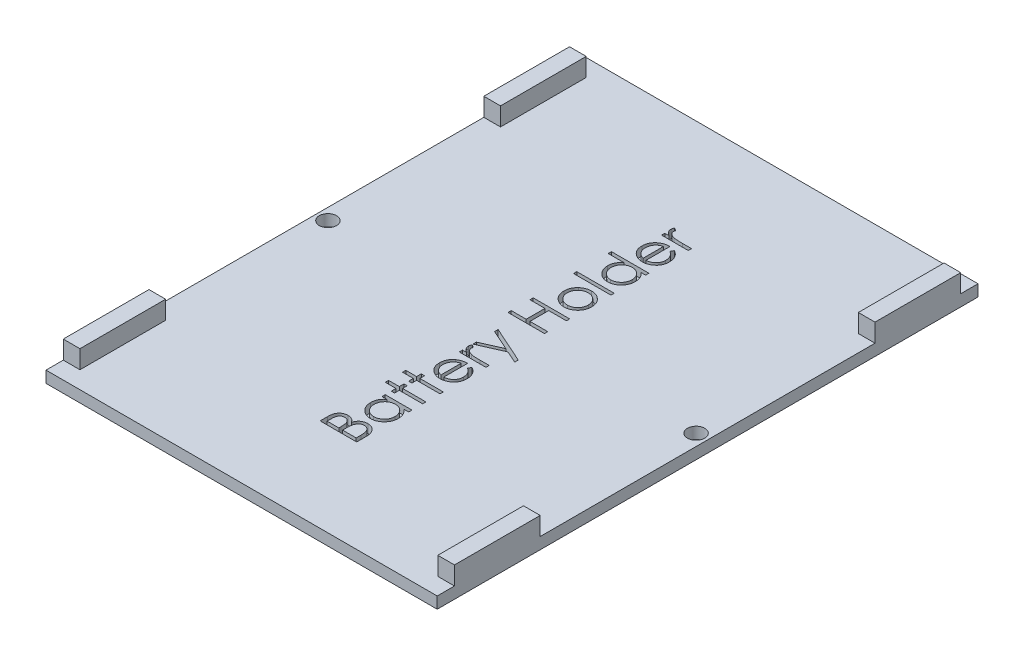
SolidWorks part; units mm, degrees
ref_plane "Front Plane" through (0, 0, 0) normal (0, 0, 1) x (1, 0, 0)
ref_plane "Top Plane" through (0, 0, 0) normal (0, 1, 0) x (1, 0, 0)
ref_plane "Right Plane" through (0, 0, 0) normal (1, 0, 0) x (0, 0, -1)
sketch "Sketch1" plane through (0, 0, 0) normal (0, 1, 0) x (1, 0, 0)
  line L1 (-34, -47) -> (34, -47)
  line L2 (-34, -47) -> (-34, 47)
  line L3 (-34, 47) -> (34, 47)
  line L4 (34, -47) -> (34, 47)
  line L5 (-34, -47) -> (34, 47) construction
  line L6 (-34, 47) -> (34, -47) construction
  point P0 (0, 0)
  dimension "D1" = 68
  dimension "D2" = 94
extrude "Boss-Extrude1" add sketch "Sketch1" along normal blind 2
sketch "Sketch2" plane through (0, 2, 0) normal (0, 1, 0) x (1, 0, 0)
  line L0 (-34, 47) -> (-34, -47) construction
  line L1 (-34, -44) -> (-31.1, -44)
  line L2 (-34, -44) -> (-34, -29.1)
  line L3 (-34, -29.1) -> (-31.1, -29.1)
  line L4 (-31.1, -44) -> (-31.1, -29.1)
  line L5 (-34, -47) -> (34, -47) construction
  dimension "D1" = 14.9
  dimension "D2" = 3
  dimension "D3" = 2.9
extrude "Boss-Extrude2" add sketch "Sketch2" along normal blind 3.175 contours L3 L4 L1 L2
mirror "Mirror1" about plane through (0, 0, 0) normal (1, 0, 0) of "Boss-Extrude2"
mirror "Mirror2" about plane through (0, 0, 0) normal (0, 0, 1) of "Mirror1"
sketch "Sketch3" plane through (0, 2, 0) normal (0, 1, 0) x (1, 0, 0)
  line L0 (3.8196, -31.6351) -> (3.8196, 31.5257) construction
  text T0 "Battery Holder" font "Century Gothic" height in points 24
  point P3 (0, 0)
  point P4 (0, 0)
extrude "Cut-Extrude1" cut sketch "Sketch3" against normal blind 1.5
sketch "Sketch4" plane through (0, 2, 0) normal (0, 1, 0) x (1, 0, 0)
  line L0 (-34, 29.1) -> (-34, -29.1) construction
  circle A0 centre (-32, 0) radius 1.5
  point P4 (0, 0)
  dimension "D2" = 3
  dimension "D1" = 2
extrude "Cut-Extrude2" cut sketch "Sketch4" against normal through all
mirror "Mirror3" about plane through (0, 0, 0) normal (1, 0, 0) of "Cut-Extrude2"
